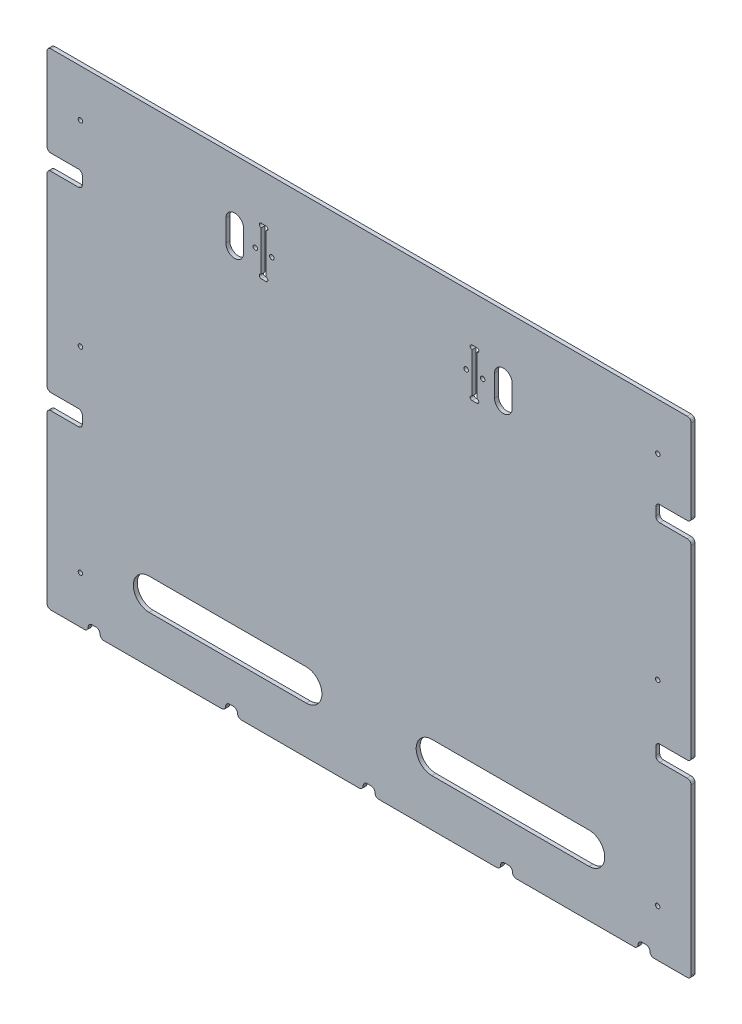
SolidWorks part; units mm, degrees
material "PC High Viscosity"
ref_plane "Front Plane" through (0, 0, 0) normal (0, 0, 1) x (1, 0, 0)
ref_plane "Top Plane" through (0, 0, 0) normal (0, 1, 0) x (1, 0, 0)
ref_plane "Right Plane" through (0, 0, 0) normal (1, 0, 0) x (0, 0, -1)
sketch "Sketch1" plane through (0, 0, 0) normal (0, 0, 1) x (1, 0, 0)
  line L1 (0, 0) -> (1041.4, 0)
  line L2 (0, 0) -> (0, 785.8125)
  line L3 (0, 785.8125) -> (1041.4, 785.8125)
  line L4 (1041.4, 0) -> (1041.4, 785.8125)
  dimension "D1" = 1041.4
  dimension "D2" = 785.8125
extrude "Boss-Extrude1" add sketch "Sketch1" along normal blind 6.35
sketch "Sketch11" plane through (0, 0, 6.35) normal (0, 0, 1) x (1, 0, 0)
  line L0 (520.7, 785.8125) -> (520.7, 0) construction
  line L1 (1041.4, 785.8125) -> (0, 785.8125) construction
  line L2 (0, 0) -> (1041.4, 0) construction
  line L3 (346.3925, 640.207) -> (346.3925, 705.2945)
  line L4 (346.3925, 711.6445) -> (354.0125, 711.6445)
  line L5 (354.0125, 705.2945) -> (354.0125, 640.207)
  line L6 (346.3925, 633.857) -> (354.0125, 633.857)
  line L7 (695.0075, 633.857) -> (687.3875, 633.857)
  line L8 (687.3875, 705.2945) -> (687.3875, 640.207)
  line L9 (695.0075, 711.6445) -> (687.3875, 711.6445)
  line L10 (695.0075, 640.207) -> (695.0075, 705.2945)
  arc A0 (346.3925, 705.2945) -> (346.3925, 711.6445) centre (346.3925, 708.4695) cw
  arc A1 (354.0125, 711.6445) -> (354.0125, 705.2945) centre (354.0125, 708.4695) cw
  arc A2 (354.0125, 640.207) -> (354.0125, 633.857) centre (354.0125, 637.032) cw
  arc A3 (346.3925, 640.207) -> (346.3925, 633.857) centre (346.3925, 637.032) ccw
  arc A4 (695.0075, 640.207) -> (695.0075, 633.857) centre (695.0075, 637.032) cw
  arc A5 (687.3875, 640.207) -> (687.3875, 633.857) centre (687.3875, 637.032) ccw
  arc A6 (687.3875, 711.6445) -> (687.3875, 705.2945) centre (687.3875, 708.4695) ccw
  arc A7 (695.0075, 705.2945) -> (695.0075, 711.6445) centre (695.0075, 708.4695) ccw
  dimension "D1" = 3.175
  dimension "D2" = 7.62
  dimension "D3" = 77.7875
  dimension "D4" = 74.168
  dimension "D5" = 333.375
extrude "Cut-Extrude5" cut sketch "Sketch11" against normal through all
hole_wizard "1/4 Clearance Hole1" positions "Sketch3" profile "Sketch4" hole size "1/4" standard "ANSI Inch" end condition through all
sketch "Sketch3" plane through (0, 0, 6.35) normal (0, 0, 1) x (1, 0, 0)
  line L1 (0, 785.8125) -> (44.45, 785.8125) construction
  line L2 (0, 785.8125) -> (0, 0) construction
  line L3 (0, 0) -> (44.45, 0) construction
  line L4 (44.45, 785.8125) -> (44.45, 0) construction
  line L5 (0, 0) -> (1041.4, 0) construction
  line L6 (1041.4, 785.8125) -> (0, 785.8125) construction
  line L7 (520.7, 785.8125) -> (520.7, 0) construction
  line L8 (350.2025, 711.6445) -> (350.2025, 633.857) construction
  line L9 (354.0125, 711.6445) -> (346.3925, 711.6445) construction
  line L10 (346.3925, 633.857) -> (354.0125, 633.857) construction
  line L11 (346.3925, 705.2945) -> (346.3925, 640.207) construction
  line L12 (1041.4, 0) -> (1041.4, 785.8125) construction
  point P79 (54.102, 76.2)
  point P83 (54.102, 392.9063)
  point P95 (987.298, 76.2)
  point P96 (987.298, 392.9062)
  point P100 (987.425, 709.6125)
  point P101 (336.8675, 672.7508)
  point P103 (363.5375, 672.7508)
  point P114 (350.2025, 672.7508)
  point P118 (677.8625, 672.7508)
  point P119 (704.5325, 672.7508)
  point P122 (54.102, 709.6125)
  dimension "D1" = 44.45
  dimension "D2" = 76.2
  dimension "D3" = 9.652
  dimension "D5" = 76.2
  dimension "D6" = 9.525
  dimension "D7" = 53.975
  dimension "D8" = 76.2
  dimension "D4" = 3
sketch "Sketch4" plane through (54.102, 709.6125, 6.35) normal (1, 0, 0) x (0, -1, 0)
  line L0 (0, 0) -> (0, 6.35)
  line L1 (0, 6.35) -> (3.5712, 6.35)
  line L2 (3.5712, 6.35) -> (3.5712, 0)
  line L5 (3.5712, 0) -> (0, 0)
  line L11 (0, -6.35) -> (0, 107.95) construction
  dimension "Thru Hole Dia." = 7.1425
  dimension "Thru Hole Depth" = 6.35
sketch "Sketch12" plane through (0, 0, 6.35) normal (0, 0, 1) x (1, 0, 0)
  line L0 (303.53, 655.2883) -> (303.53, 690.2133) construction
  line L1 (289.2425, 655.2883) -> (289.2425, 690.2133)
  line L2 (317.8175, 655.2883) -> (317.8175, 690.2133)
  line L3 (520.7, 785.8125) -> (520.7, 0) construction
  line L4 (1041.4, 785.8125) -> (0, 785.8125) construction
  line L5 (0, 0) -> (1041.4, 0) construction
  line L6 (737.87, 655.2883) -> (737.87, 690.2133) construction
  line L7 (752.1575, 655.2883) -> (752.1575, 690.2133)
  line L8 (723.5825, 655.2883) -> (723.5825, 690.2133)
  arc A0 (289.2425, 655.2883) -> (317.8175, 655.2883) centre (303.53, 655.2883) ccw
  arc A1 (317.8175, 690.2133) -> (289.2425, 690.2133) centre (303.53, 690.2133) ccw
  circle A2 centre (336.8675, 672.7508) radius 3.5712 construction
  circle A3 centre (336.8675, 672.7508) radius 3.5712 construction
  arc A4 (752.1575, 655.2883) -> (723.5825, 655.2883) centre (737.87, 655.2883) cw
  arc A5 (723.5825, 690.2133) -> (752.1575, 690.2133) centre (737.87, 690.2133) cw
  point P2 (303.53, 672.7508)
  point P12 (737.87, 672.7508)
  dimension "D1" = 28.575
  dimension "D2" = 63.5
  dimension "D3" = 19.05
extrude "Cut-Extrude6" cut sketch "Sketch12" against normal through all
ref_plane "Plane1" through (520.7, 0, 0) normal (1, 0, 0) x (0, 0, -1)
sketch "Sketch13" plane through (0, 0, 0) normal (0, 0, -1) x (-1, 0, 0)
  line L0 (-1041.4, 639.7625) -> (-1041.4, 614.3625)
  line L1 (-1041.4, 639.7625) -> (-984.25, 639.7625)
  line L2 (-1041.4, 614.3625) -> (-984.25, 614.3625)
  line L3 (-984.25, 639.7625) -> (-984.25, 614.3625)
  line L4 (-1041.4, 0) -> (-1041.4, 785.8125) construction
  line L5 (-1041.4, 304.4825) -> (-1041.4, 279.0825)
  line L6 (-1041.4, 304.4825) -> (-984.25, 304.4825)
  line L7 (-1041.4, 279.0825) -> (-984.25, 279.0825)
  line L8 (-984.25, 304.4825) -> (-984.25, 279.0825)
  line L9 (-1041.4, 785.8125) -> (0, 785.8125) construction
  point P11 (-984.25, 627.0625)
  dimension "D1" = 158.75
  dimension "D2" = 335.28
  dimension "D3" = 25.4
  dimension "D4" = 57.15
extrude "Cut-Extrude7" cut sketch "Sketch13" against normal through all
fillet "Fillet1" radius 6.35 4 edges at (984.25, 639.7625, 3.175) (984.25, 614.3625, 3.175) (984.25, 279.0825, 3.175) (984.25, 304.4825, 3.175)
mirror "Mirror1" about plane through (520.7, 0, 0) normal (1, 0, 0) of "Fillet1", "Cut-Extrude7"
sketch "Sketch16" plane through (0, 0, 6.35) normal (0, 0, 1) x (1, 0, 0)
  line L0 (66.675, 0) -> (85.725, 0)
  line L1 (66.675, 0) -> (66.675, 6.35)
  line L2 (85.725, 0) -> (85.725, 6.35)
  line L3 (73.025, 12.7) -> (79.375, 12.7)
  line L4 (0, 0) -> (1041.4, 0) construction
  line L5 (0, 279.0825) -> (0, 0) construction
  arc A0 (85.725, 6.35) -> (79.375, 12.7) centre (79.375, 6.35) ccw
  arc A1 (73.025, 12.7) -> (66.675, 6.35) centre (73.025, 6.35) ccw
  dimension "D1" = 6.35
  dimension "D2" = 12.7
  dimension "D3" = 19.05
  dimension "D4" = 66.675
extrude "Cut-Extrude8" cut sketch "Sketch16" against normal through all
pattern_linear "LPattern1" count 5 spacing 222.25 along (1, 0, 0) of "Cut-Extrude8"
sketch "Sketch17" plane through (0, 0, 6.35) normal (0, 0, 1) x (1, 0, 0)
  line L0 (419.1, 101.6) -> (165.1, 101.6) construction
  line L1 (419.1, 76.2) -> (165.1, 76.2)
  line L2 (419.1, 127) -> (165.1, 127)
  line L3 (1041.4, 785.8125) -> (0, 785.8125) construction
  line L4 (307.975, 0) -> (511.175, 0) construction
  arc A0 (419.1, 76.2) -> (419.1, 127) centre (419.1, 101.6) ccw
  arc A1 (165.1, 127) -> (165.1, 76.2) centre (165.1, 101.6) ccw
  point P2 (292.1, 101.6)
  point P9 (520.7, 785.8125)
  dimension "D1" = 254
  dimension "D2" = 228.6
  dimension "D3" = 50.8
  dimension "D4" = 101.6
extrude "Cut-Extrude9" cut sketch "Sketch17" against normal through all
pattern_linear "LPattern2" count 2 spacing 457.2 along (1, 0, 0) of "Cut-Extrude9"
fillet "Fillet2" radius 6.35 22 edges at (0, 785.8125, 3.175) (0, 639.7625, 3.175) (0, 614.3625, 3.175) (0, 304.4825, 3.175) (0, 279.0825, 3.175) (0, 0, 3.175) (66.675, 0, 3.175) (85.725, 0, 3.175) (288.925, 0, 3.175) (307.975, 0, 3.175) (511.175, 0, 3.175) (530.225, 0, 3.175) (733.425, 0, 3.175) (752.475, 0, 3.175) (955.675, 0, 3.175) (974.725, 0, 3.175) (1041.4, 0, 3.175) (1041.4, 279.0825, 3.175) (1041.4, 304.4825, 3.175) (1041.4, 614.3625, 3.175) (1041.4, 639.7625, 3.175) (1041.4, 785.8125, 3.175)
